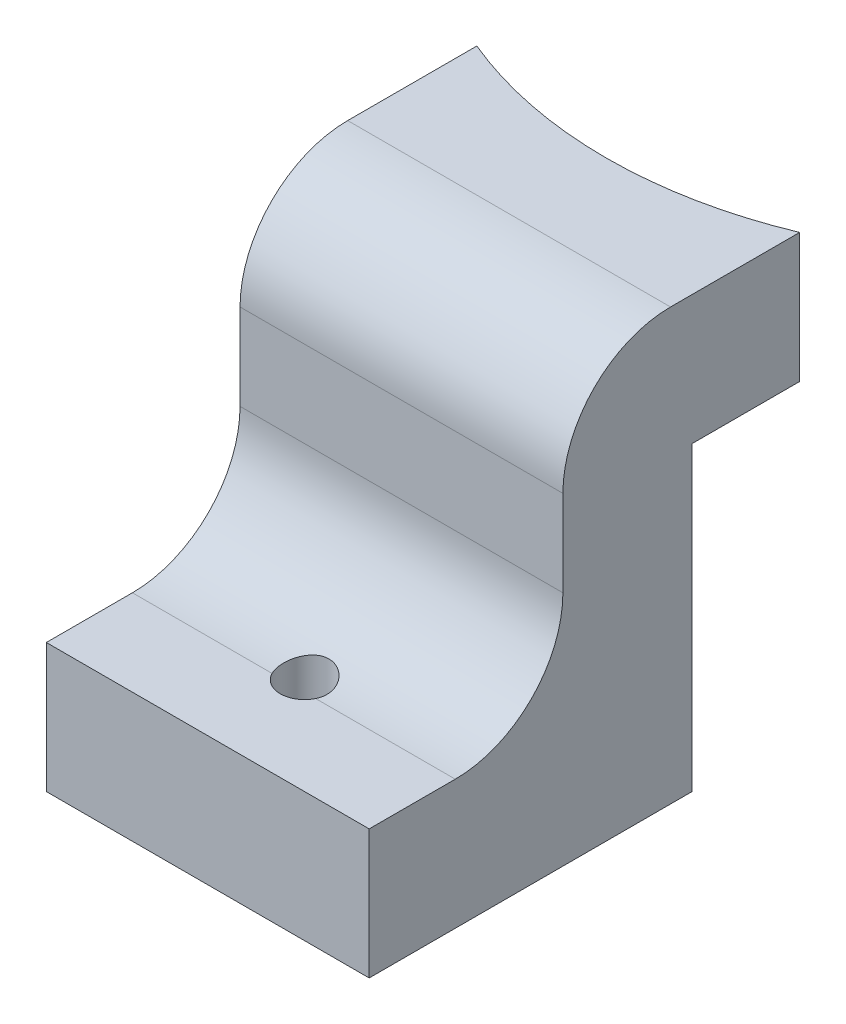
SolidWorks part; units mm, degrees
material "6061 Alloy"
ref_plane "Front Plane" through (0, 0, 0) normal (0, 0, 1) x (1, 0, 0)
ref_plane "Top Plane" through (0, 0, 0) normal (0, 1, 0) x (1, 0, 0)
ref_plane "Right Plane" through (0, 0, 0) normal (1, 0, 0) x (0, 0, -1)
sketch "Sketch1" plane through (0, 0, 0) normal (0, 1, 0) x (1, 0, 0)
  line L0 (7.5, 5) -> (-7.5, -5) construction
  line L1 (-7.5, 5) -> (7.5, 5)
  line L2 (-7.5, 5) -> (-7.5, -5)
  line L3 (-7.5, -5) -> (7.5, -5)
  line L4 (7.5, 5) -> (7.5, -5)
  line L5 (-7.5, 5) -> (7.5, -5) construction
  point P2 (0, 0)
  dimension "D1" = 15
  dimension "D2" = 10
extrude "Boss-Extrude1" add sketch "Sketch1" along normal blind 6
sketch "Sketch2" plane through (0, 6, 0) normal (0, 1, 0) x (1, 0, 0)
  circle A0 centre (0, 23) radius 19.5
  dimension "D1" = 39
extrude "Cut-Extrude1" cut sketch "Sketch2" against normal blind 9
sketch "Sketch3" plane through (0, 6, 0) normal (0, 1, 0) x (1, 0, 0)
  line L0 (-7.5, 5) -> (-7.5, -5) construction
  line L1 (-7.5, 0) -> (7.5, 0)
  line L2 (-7.5, 0) -> (-7.5, -6)
  line L3 (-7.5, -6) -> (7.5, -6)
  line L4 (7.5, 0) -> (7.5, -6)
  line L5 (-7.5, -5) -> (7.5, -5) construction
  line L6 (7.5, -5) -> (7.5, 5) construction
  dimension "D1" = 5
  dimension "D2" = 0
  dimension "D3" = 15
  dimension "D4" = 6
extrude "Boss-Extrude2" add sketch "Sketch3" against normal blind 20
sketch "Sketch4" plane through (0, 0, 6) normal (0, 0, 1) x (1, 0, 0)
  line L0 (-7.5, -14) -> (7.5, -14) construction
  line L1 (-7.5, -8) -> (7.5, -8)
  line L2 (-7.5, -8) -> (-7.5, -14)
  line L3 (-7.5, -14) -> (7.5, -14)
  line L4 (7.5, -8) -> (7.5, -14)
  line L5 (7.5, -14) -> (7.5, 6) construction
  line L6 (-7.5, -14) -> (-7.5, 6) construction
  dimension "D1" = 6
  dimension "D3" = 0
extrude "Boss-Extrude3" add sketch "Sketch4" along normal blind 9
sketch "Sketch9" plane through (0, -14, 0) normal (0, -1, 0) x (1, 0, 0)
  line L0 (0, 15) -> (0, 0) construction
  line L1 (-7.5, 15) -> (7.5, 15) construction
  line L2 (7.5, 0) -> (-7.5, 0) construction
  line L3 (-7.5, 10.5) -> (7.5, 10.5) construction
  line L4 (-7.5, 0) -> (-7.5, 15) construction
  line L5 (7.5, 15) -> (7.5, 0) construction
  point P12 (0, 10.5)
  dimension "D1" = 4.5
hole_wizard "#4-40 Tapped Hole2" positions "Sketch10" profile "Sketch11" tap size "#4-40" standard "ANSI Inch"
sketch "Sketch10" plane through (0, -14, 0) normal (0, -1, 0) x (-1, 0, 0)
  point P0 (0, -10.5)
sketch "Sketch11" plane through (0, -14, 10.5) normal (1, 0, 0) x (0, 0, -1)
  line L0 (0, 0) -> (0, 8.2792)
  line L1 (0, 8.2792) -> (1.1303, 7.6)
  line L2 (1.1303, 7.6) -> (1.1303, 0)
  line L5 (1.1303, 0) -> (0, 0)
  line L10 (0, 8.2792) -> (-1.1303, 7.6) construction
  line L11 (0, -6.35) -> (0, 107.95) construction
  dimension "Tap Drill Dia." = 2.2606
  dimension "Tap Drill Depth" = 7.6
  dimension "Drill Angle" = 118
cosmetic thread "Hole Thread2" parameters "D1"=5.69, "D2"=2.8448
fillet "Fillet2" radius 5 2 edges at (0, 6, 6) (0, -8, 6)
